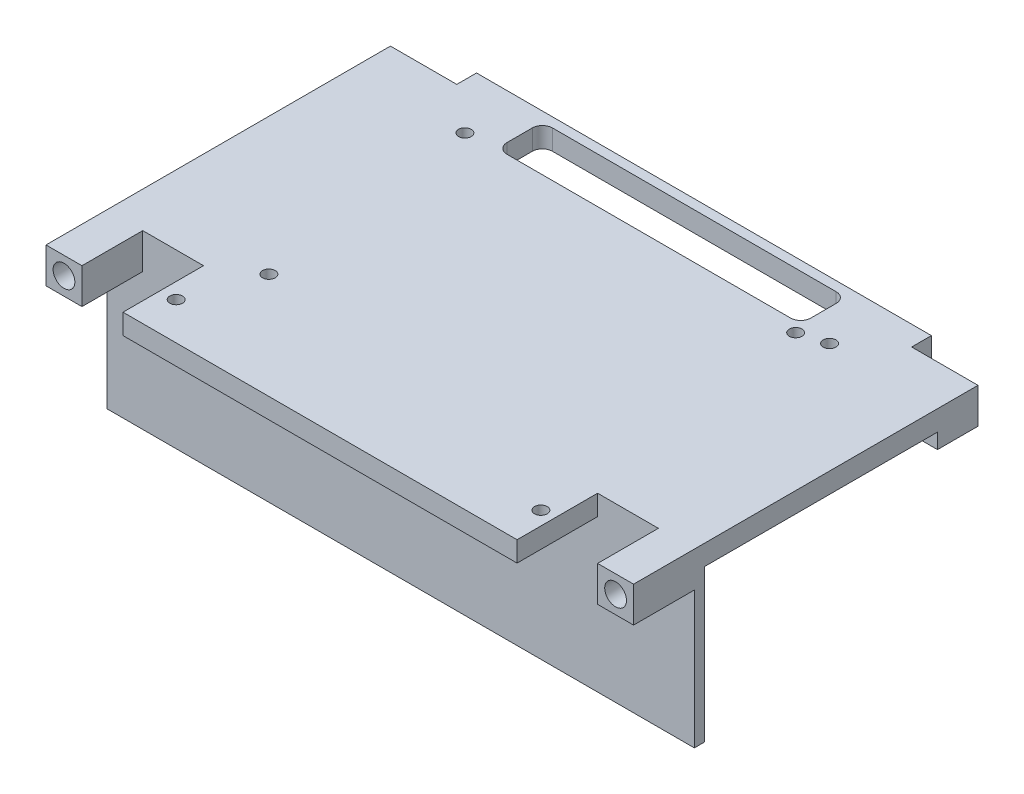
SolidWorks part; units mm, degrees
ref_plane "Front Plane" through (0, 0, 0) normal (0, 0, 1) x (1, 0, 0)
ref_plane "Top Plane" through (0, 0, 0) normal (0, 1, 0) x (1, 0, 0)
ref_plane "Right Plane" through (0, 0, 0) normal (1, 0, 0) x (0, 0, -1)
sketch "Sketch1" plane through (0, 0, 0) normal (0, 1, 0) x (1, 0, 0)
  line L0 (-58, 0) -> (58, 0) construction
  line L1 (-58, -34) -> (-50.9, -34)
  line L2 (-58, -34) -> (-58, 34)
  line L3 (-58, 34) -> (-50.9, 34)
  line L4 (58, -34) -> (58, 34)
  line L5 (-58, -34) -> (58, 34) construction
  line L6 (-58, 34) -> (58, -34) construction
  line L8 (-50.9, 34) -> (-50.9, 41)
  line L9 (-50.9, 41) -> (50.9, 41)
  line L10 (50.9, 34) -> (50.9, 41)
  line L11 (50.9, 34) -> (58, 34)
  line L12 (50.9, -34) -> (50.9, -41)
  line L13 (-50.9, -41) -> (50.9, -41)
  line L14 (-50.9, -34) -> (-50.9, -41)
  line L15 (50.9, -34) -> (58, -34)
  point P0 (0, 0)
  point P10 (0, 41)
  dimension "D1" = 116
  dimension "D2" = 68
  dimension "D3" = 7.1
  dimension "D4" = 7
extrude "Boss-Extrude1" add sketch "Sketch1" along normal blind 4
sketch "Sketch3" plane through (0, 0, 0) normal (0, -1, 0) x (1, 0, 0)
  line L0 (-58, -34) -> (-58, 34) construction
  line L1 (-50.9, -34) -> (-58, -34)
  line L2 (-50.9, -34) -> (-50.9, -26)
  line L3 (-50.9, -26) -> (-58, -26)
  line L4 (-58, -34) -> (-58, -26)
  dimension "D1" = 8
extrude "Boss-Extrude3" add sketch "Sketch3" along normal blind 3
sketch "Sketch4" plane through (0, 0, -34) normal (0, 0, -1) x (-1, 0, 0)
  line L0 (58, -3) -> (50.9, 4) construction
  circle A0 centre (54.45, 0.5) radius 2.15
  dimension "D1" = 4.3
extrude "Cut-Extrude1" cut sketch "Sketch4" against normal blind 7
mirror "Mirror1" about plane through (0, 0, 0) normal (1, 0, 0) of "Cut-Extrude1", "Boss-Extrude3"
mirror "Mirror2" about plane through (0, 0, 0) normal (0, 0, 1) of "Cut-Extrude1", "Boss-Extrude3", "Mirror1"
sketch "Sketch5" plane through (0, 4, 0) normal (0, 1, 0) x (1, 0, 0)
  line L0 (50.9, 41) -> (-50.9, 41) construction
  line L1 (-30, 36) -> (30, 36)
  line L2 (-30, 36) -> (-30, 27)
  line L3 (-30, 27) -> (30, 27)
  line L4 (30, 36) -> (30, 27)
  point P4 (0, 27)
  dimension "D1" = 5
  dimension "D2" = 9
  dimension "D3" = 60
extrude "Cut-Extrude2" cut sketch "Sketch5" against normal through all
sketch "Sketch6" plane through (0, 4, 0) normal (0, 1, 0) x (1, 0, 0)
  line L1 (-38.5, -28) -> (38.5, -28) construction
  line L2 (-38.5, -28) -> (-38.5, 24) construction
  line L3 (-38.5, 24) -> (38.5, 24) construction
  line L4 (38.5, -28) -> (38.5, 24) construction
  line L5 (-38.5, -28) -> (38.5, 24) construction
  line L6 (-38.5, 24) -> (38.5, -28) construction
  circle A0 centre (-38.5, 24) radius 1.25
  circle A1 centre (38.5, 24) radius 1.25
  circle A2 centre (38.5, -28) radius 1.25
  circle A3 centre (-38.5, -28) radius 1.25
  point P0 (0, -2)
  point P9 (0, -2)
  dimension "D4" = 2.5
  dimension "D1" = 77
  dimension "D2" = 52
  dimension "D3" = 2
fillet "Fillet1" radius 2 4 edges at (-30, 2, -36) (-30, 2, -27) (30, 2, -36) (30, 2, -27)
sketch "Sketch7" plane through (0, 4, 0) normal (0, 1, 0) x (1, 0, 0)
  line L0 (50.9, 34) -> (50.9, 41) construction
  line L1 (-50.9, 41) -> (50.9, 41)
  line L2 (-50.9, 41) -> (-50.9, 40)
  line L3 (-50.9, 40) -> (50.9, 40)
  line L4 (50.9, 41) -> (50.9, 40)
  line L5 (-50.9, -34) -> (-50.9, -41) construction
  line L6 (50.9, -41) -> (-50.9, -41)
  line L7 (50.9, -41) -> (50.9, -40)
  line L8 (50.9, -40) -> (-50.9, -40)
  line L9 (-50.9, -41) -> (-50.9, -40)
  dimension "D1" = 1
  dimension "D2" = 1
extrude "Cut-Extrude3" cut sketch "Sketch7" against normal through all
sketch "Sketch8" plane through (0, 0, 0) normal (0, -1, 0) x (1, 0, 0)
  line L0 (58, 26) -> (58, -26) construction
  line L1 (58, 22) -> (-58, 22)
  line L2 (58, 22) -> (58, 20)
  line L3 (58, 20) -> (-58, 20)
  line L4 (-58, 22) -> (-58, 20)
  line L5 (-58, -26) -> (-58, 26) construction
  line L7 (50.9, 40) -> (-50.9, 40) construction
  dimension "D1" = 20
  dimension "D2" = 2
extrude "Boss-Extrude4" add sketch "Sketch8" along normal blind 30
sketch "Sketch9" plane through (0, 4, 0) normal (0, 1, 0) x (1, 0, 0)
  line L0 (58, -22) -> (-58, -22) construction
  line L1 (-50.9, -40) -> (-38.9, -40)
  line L2 (-50.9, -40) -> (-50.9, -22)
  line L3 (-50.9, -22) -> (-38.9, -22)
  line L4 (-38.9, -40) -> (-38.9, -22)
  dimension "D1" = 12
extrude "Cut-Extrude4" cut sketch "Sketch9" against normal blind 10
sketch "Sketch10" plane through (0, -3, 0) normal (0, -1, 0) x (1, 0, 0)
  line L1 (-58, 26) -> (-50.9, 26)
  line L2 (-58, 26) -> (-58, 22)
  line L3 (-58, 22) -> (-50.9, 22)
  line L4 (-50.9, 26) -> (-50.9, 22)
  line L5 (50.9, 26) -> (58, 26)
  line L6 (50.9, 26) -> (50.9, 22)
  line L7 (50.9, 22) -> (58, 22)
  line L8 (58, 26) -> (58, 22)
extrude "Boss-Extrude5" add sketch "Sketch10" against normal up to surface (3 mm away) up to face at (27.2714, 0, 30)
ref_plane "Plane2" through (-51, 0, 0) normal (-1, 0, 0) x (0, 0, 1)
sketch "Sketch12" plane through (-51, 0, 0) normal (-1, 0, 0) x (0, 0, 1)
  line L0 (22, -5.8) -> (22, -16.2)
  line L1 (22, -30) -> (22, -3) construction
  line L2 (22, -16.2) -> (24.7, -13.5)
  line L3 (24.7, -13.5) -> (24.7, -8.5)
  line L4 (24.7, -8.5) -> (22, -5.8)
  line L5 (24.7, -11) -> (22, -11) construction
  line L6 (22, -3) -> (34, -3) construction
  line L7 (24.1, -9) -> (22.6, -9)
  line L8 (24.1, -9) -> (24.1, -13)
  line L9 (24.1, -13) -> (22.6, -13)
  line L10 (22.6, -9) -> (22.6, -13)
  line L11 (22, -20.8) -> (22, -31.2)
  line L12 (22, -31.2) -> (24.7, -28.5)
  line L13 (24.7, -28.5) -> (24.7, -23.5)
  line L14 (24.7, -23.5) -> (22, -20.8)
  line L15 (24.1, -24) -> (22.6, -24)
  line L16 (24.1, -24) -> (24.1, -28)
  line L17 (24.1, -28) -> (22.6, -28)
  line L18 (22.6, -24) -> (22.6, -28)
  line L19 (24.7, -26) -> (22, -26) construction
  point P13 (23.35, -11)
  point P14 (24.1, -11)
  dimension "D1" = 1.5
  dimension "D2" = 0.6
  dimension "D3" = 0.6
  dimension "D4" = 4
  dimension "D5" = 45
  dimension "D6" = 5
  dimension "D7" = 8
  dimension "D8" = 2
extrude "Boss-Extrude6" add sketch "Sketch12" against normal blind 2
ref_plane "Plane3" through (-44.9, 0, 0) normal (1, 0, 0) x (0, 0, -1)
mirror "Mirror3" about plane through (-44.9, 0, 0) normal (1, 0, 0) of "Boss-Extrude6"
sketch "Sketch13" plane through (0, 0, 0) normal (0, -1, 0) x (1, 0, 0)
  line L0 (-28, -27) -> (28, -27) construction
  line L1 (-18, -17.5) -> (18, -17.5)
  line L2 (-18, -17.5) -> (-18, -19.5)
  line L3 (-18, -19.5) -> (18, -19.5)
  line L4 (18, -17.5) -> (18, -19.5)
  point P4 (0, -19.5)
  dimension "D1" = 36
  dimension "D2" = 2
  dimension "D3" = 7.5
extrude "Boss-Extrude7" add sketch "Sketch13" along normal up to surface (30 mm away) up to face at (-22.45, -30, 21.5)
sketch "Sketch14" plane through (0, 0, 0) normal (1, 0, 0) x (0, 0, -1)
  line L3 (-0.25, -38) -> (-0.25, 0) construction
  line L4 (-20, 0) -> (26, 0) construction
  line L13 (-24.1, -13) -> (-24.1, -9) construction
  line L14 (-24.1, -9) -> (-22.6, -9) construction
  line L15 (-22.6, -9) -> (-22.6, -13) construction
  line L16 (-22.6, -13) -> (-24.1, -13) construction
  line L17 (-22, -5.8) -> (-22, -16.2) construction
  line L18 (-22, -16.2) -> (-24.7, -13.5) construction
  line L19 (-24.7, -13.5) -> (-24.7, -8.5) construction
  line L20 (-24.7, -8.5) -> (-22, -5.8) construction
  line L29 (-24.1, -13) -> (-24.1, -9) construction
  line L30 (-24.1, -9) -> (-22.6, -9) construction
  line L31 (-22.6, -9) -> (-22.6, -13) construction
  line L32 (-22.6, -13) -> (-24.1, -13) construction
  line L33 (-22, -5.8) -> (-22, -16.2) construction
  line L34 (-22, -16.2) -> (-24.7, -13.5) construction
  line L35 (-24.7, -13.5) -> (-24.7, -8.5) construction
  line L36 (-24.7, -8.5) -> (-22, -5.8) construction
  line L37 (24.2, -8.5) -> (21.5, -5.8)
  line L38 (24.2, -13.5) -> (24.2, -8.5)
  line L39 (21.5, -16.2) -> (24.2, -13.5)
  line L40 (21.5, -5.8) -> (21.5, -16.2)
  line L41 (22.1, -13) -> (23.6, -13)
  line L42 (22.1, -9) -> (22.1, -13)
  line L43 (23.6, -9) -> (22.1, -9)
  line L44 (23.6, -13) -> (23.6, -9)
extrude "Boss-Extrude8" add sketch "Sketch14" along normal mid plane 2
sketch "Sketch15" plane through (0, 0, 0) normal (1, 0, 0) x (0, 0, -1)
  line L0 (17.5, 0) -> (17.5, -5)
  line L1 (17.5, -30) -> (17.5, 0) construction
  line L2 (17.5, -5) -> (14.6132, 0)
  line L3 (-20, 0) -> (26, 0) construction
  line L4 (14.6132, 0) -> (17.5, 0)
  dimension "D1" = 60
  dimension "D2" = 5
extrude "Boss-Extrude9" add sketch "Sketch15" against normal up to surface and the other way up to surface up to face at (-18, -15, -18.5) other way up to face at (18, -15, -18.5)
sketch "Sketch16" plane through (0, 0, 40) normal (0, 0, 1) x (1, 0, 0)
  line L0 (38, 0) -> (18, -28) construction
  line L1 (38, 0) -> (18, 0)
  line L2 (38, 0) -> (38, -28)
  line L3 (38, -28) -> (18, -28)
  line L4 (18, 0) -> (18, -28)
  line L5 (50.9, 0) -> (-38.9, 0) construction
  line L6 (20.7, -15.8) -> (35.3, -15.8)
  line L7 (20.7, -15.8) -> (20.7, -25)
  line L8 (20.7, -25) -> (35.3, -25)
  line L9 (35.3, -15.8) -> (35.3, -25)
  line L10 (20.7, -15.8) -> (35.3, -25) construction
  line L11 (20.7, -25) -> (35.3, -15.8) construction
  line L12 (58, -30) -> (58, -3) construction
  point P5 (28, -14)
  point P10 (28, -20.4)
  dimension "D1" = 20
  dimension "D2" = 28
  dimension "D3" = 14.6
  dimension "D4" = 9.2
  dimension "D5" = 20
  dimension "D6" = 3
extrude "Boss-Extrude10" add sketch "Sketch16" against normal blind 2.6
sketch "Sketch17" plane through (0, 0, 0) normal (0, -1, 0) x (1, 0, 0)
  line L6 (-38.9, 22) -> (-50.9, 22) construction
  line L7 (50.9, 40) -> (38.9, 40)
  line L8 (50.9, 40) -> (50.9, 22)
  line L9 (50.9, 22) -> (38.9, 22)
  line L10 (38.9, 40) -> (38.9, 22)
  line L13 (-38.9, 40) -> (-38.9, 22) construction
extrude "Cut-Extrude5" cut sketch "Sketch17" against normal through all
sketch "Sketch18" plane through (0, 4, 0) normal (0, 1, 0) x (1, 0, 0)
  line L5 (-50.9, 40) -> (50.9, 40) construction
  line L6 (50.9, 34) -> (44.9, 34)
  line L7 (50.9, 34) -> (50.9, 40)
  line L8 (50.9, 40) -> (44.9, 40)
  line L9 (44.9, 34) -> (44.9, 40)
  line L11 (-50.9, 34) -> (-44.9, 34)
  line L12 (-50.9, 34) -> (-50.9, 40)
  line L13 (-50.9, 40) -> (-44.9, 40)
  line L14 (-44.9, 34) -> (-44.9, 40)
extrude "Cut-Extrude6" cut sketch "Sketch18" against normal through all
sketch "Sketch20" plane through (0, 4, 0) normal (0, 1, 0) x (1, 0, 0)
  line L0 (-31, 25) -> (31, -17) construction
  line L1 (-31, 25) -> (31, 25) construction
  line L2 (-31, 25) -> (-31, -17) construction
  line L3 (-31, -17) -> (31, -17) construction
  line L4 (31, 25) -> (31, -17) construction
  line L5 (-38.5, 26) -> (38.5, 26) construction
  line L6 (-38.5, 26) -> (-38.5, -26) construction
  line L7 (-38.5, -26) -> (38.5, -26) construction
  line L8 (38.5, 26) -> (38.5, -26) construction
  line L11 (38.5, 26) -> (-38.5, -26) construction
  circle A0 centre (-31, 25) radius 3 construction
  circle A1 centre (-31, -17) radius 3 construction
  circle A2 centre (31, -17) radius 3 construction
  circle A3 centre (31, 25) radius 3 construction
  circle A4 centre (-38.5, 26) radius 3 construction
  circle A5 centre (38.5, 26) radius 3 construction
  circle A6 centre (38.5, -26) radius 3 construction
  circle A7 centre (-38.5, -26) radius 3 construction
  point P18 (0, 4)
  dimension "D3" = 6
  dimension "D1" = 42
  dimension "D2" = 62
  dimension "D4" = 4
  dimension "D6" = 77
  dimension "D7" = 52
sketch "Sketch22" plane through (0, 4, 0) normal (0, 1, 0) x (1, 0, 0)
  circle A0 centre (-31, 25) radius 1.25 construction
  circle A1 centre (31, 25) radius 1.25
  circle A2 centre (31, -17) radius 1.25 construction
  circle A3 centre (-31, -17) radius 1.25
  dimension "D1" = 2.5
extrude "Cut-Extrude7" cut sketch "Sketch22" against normal up to surface (4 mm away) up to face at (14, 0, 34.85)
sketch "Sketch25" plane through (0, 0, -19.5) normal (0, 0, -1) x (-1, 0, 0)
  line L0 (58, -30) -> (-58, -30) construction
  line L1 (-18, -30) -> (-12, -30)
  line L2 (-18, -30) -> (-18, 0)
  line L3 (-18, 0) -> (-12, 0)
  line L4 (-12, -30) -> (-12, 0)
  line L5 (-18, -30) -> (-18, 0) construction
  line L6 (18, 0) -> (-18, 0) construction
  line L7 (-18, -30) -> (18, -30) construction
  line L8 (18, 0) -> (12, 0)
  line L9 (18, 0) -> (18, -30)
  line L10 (18, -30) -> (12, -30)
  line L11 (12, 0) -> (12, -30)
  dimension "D1" = 6
extrude "Cut-Extrude11" cut sketch "Sketch25" against normal blind 10
sketch "Sketch26" plane through (-1, 0, 0) normal (-1, 0, 0) x (0, 0, 1)
  line L1 (-20.3582, -5.0992) -> (-27.2016, -5.0992)
  line L2 (-20.3582, -5.0992) -> (-20.3582, -36.3625)
  line L3 (-20.3582, -36.3625) -> (-27.2016, -36.3625)
  line L4 (-27.2016, -5.0992) -> (-27.2016, -36.3625)
  line L5 (22, -5.8) -> (28.5342, -5.8)
  line L6 (22, -5.8) -> (22, -34.3243)
  line L7 (22, -34.3243) -> (28.5342, -34.3243)
  line L8 (28.5342, -5.8) -> (28.5342, -34.3243)
extrude "Cut-Extrude12" cut sketch "Sketch26" against normal through all both and the other way through all
sketch "Sketch27" plane through (0, 4, 0) normal (0, 1, 0) x (1, 0, 0)
  line L1 (-35.8, -30.5) -> (36.2, -30.5) construction
  line L2 (-35.8, -30.5) -> (-35.8, 26.5) construction
  line L3 (-35.8, 26.5) -> (36.2, 26.5) construction
  line L4 (36.2, -30.5) -> (36.2, 26.5) construction
  line L5 (-35.8, -30.5) -> (36.2, 26.5) construction
  line L6 (-35.8, 26.5) -> (36.2, -30.5) construction
  circle A0 centre (-35.8, 26.5) radius 1.25
  circle A1 centre (-35.8, -30.5) radius 1.25
  circle A2 centre (36.2, -30.5) radius 1.25
  circle A3 centre (36.2, 26.5) radius 1.25
  circle A5 centre (31, 25) radius 1.25 construction
  circle A6 centre (31, 25) radius 1.25 construction
  point P0 (0.2, -2)
  dimension "D1" = 72
  dimension "D2" = 57
  dimension "D3" = 2
  dimension "D4" = 0.2
extrude "Cut-Extrude13" cut sketch "Sketch27" against normal through all
sketch "Sketch28" plane through (0, 4, 0) normal (0, 1, 0) x (1, 0, 0)
  line L0 (44.9, 40) -> (44.9, 34) construction
  line L1 (-44.9, 40) -> (44.9, 40)
  line L2 (-44.9, 40) -> (-44.9, 39.4)
  line L3 (-44.9, 39.4) -> (44.9, 39.4)
  line L4 (44.9, 40) -> (44.9, 39.4)
  line L5 (-38.9, -40) -> (-38.9, -22) construction
  line L6 (38.9, -40) -> (-38.9, -40)
  line L7 (38.9, -40) -> (38.9, -39.4)
  line L8 (38.9, -39.4) -> (-38.9, -39.4)
  line L9 (-38.9, -40) -> (-38.9, -39.4)
  dimension "D1" = 0.6
  dimension "D2" = 0.6
extrude "Cut-Extrude14" cut sketch "Sketch28" against normal through all
chamfer "Chamfer1" distance 2 angle 45 1 edges at (28, 0, 37.4)
sketch "Sketch29" plane through (0, 0, 39.4) normal (0, 0, 1) x (1, 0, 0)
  line L1 (18, -28) -> (38, -28)
  line L2 (18, -28) -> (18, 0)
  line L3 (18, 0) -> (38, 0)
  line L4 (38, -28) -> (38, 0)
extrude "Cut-Extrude15" cut sketch "Sketch29" against normal up to surface (17.4 mm away) up to face at (0, -4.6667, 22)
sketch "Sketch30" plane through (0, 4, 0) normal (0, 1, 0) x (1, 0, 0)
  line L0 (44.9, 39.4) -> (44.9, 34) construction
  line L1 (-44.9, 39.4) -> (44.9, 39.4)
  line L2 (-44.9, 39.4) -> (-44.9, 37.9)
  line L3 (-44.9, 37.9) -> (44.9, 37.9)
  line L4 (44.9, 39.4) -> (44.9, 37.9)
  line L5 (-38.9, -39.4) -> (-38.9, -22) construction
  line L6 (38.9, -39.4) -> (-38.9, -39.4)
  line L7 (38.9, -39.4) -> (38.9, -37.9)
  line L8 (38.9, -37.9) -> (-38.9, -37.9)
  line L9 (-38.9, -39.4) -> (-38.9, -37.9)
  dimension "D1" = 1.5
  dimension "D2" = 1.5
sketch "Sketch31" plane through (-1, 0, 0) normal (-1, 0, 0) x (0, 0, 1)
  line L4 (-24.2, -8.5) -> (-24.2, -13.5)
  line L5 (-24.2, -13.5) -> (-21.5, -16.2)
  line L6 (-21.5, -16.2) -> (-21.5, -5.8)
  line L7 (-21.5, -5.8) -> (-24.2, -8.5)
  line L8 (-24.2, -8.5) -> (-24.2, -13.5)
  line L9 (-24.2, -13.5) -> (-21.5, -16.2)
  line L10 (-21.5, -16.2) -> (-21.5, -5.8)
  line L11 (-21.5, -5.8) -> (-24.2, -8.5)
  dimension "D1" = 0
extrude "Cut-Extrude16" cut sketch "Sketch31" against normal up to surface (2 mm away) up to face at (1, -11, -22.85)
extrude "Cut-Extrude17" cut sketch "Sketch30" against normal through all
sketch "Sketch32" plane through (0, 0, -19.5) normal (0, 0, -1) x (-1, 0, 0)
  line L0 (44.9, 0) -> (-44.9, 0) construction
  line L1 (-7, -12) -> (7, -12)
  line L2 (-7, -12) -> (-7, -18)
  line L3 (-7, -18) -> (7, -18)
  line L4 (7, -12) -> (7, -18)
  point P4 (0, -12)
  dimension "D1" = 14
  dimension "D2" = 6
  dimension "D3" = 12
extrude "Boss-Extrude11" add sketch "Sketch32" along normal blind 1
chamfer "Chamfer2" distance 1 angle 45 1 edges at (0, -12, -19.5)
sketch "Sketch33" plane through (0, 0, -20.5) normal (0, 0, -1) x (-1, 0, 0)
  line L0 (-7, -12) -> (7, -18) construction
  line L1 (-4, -15) -> (4, -15) construction
  circle A0 centre (4, -15) radius 1.65
  circle A1 centre (-4, -15) radius 1.65
  point P7 (0, -15)
  dimension "D2" = 3.3
  dimension "D1" = 8
sketch "Sketch34" plane through (0, 0, -17.5) normal (0, 0, 1) x (1, 0, 0)
  line L4 (7, -18) -> (7, -12)
  line L5 (-7, -18) -> (7, -18)
  line L6 (-7, -12) -> (-7, -18)
  line L7 (7, -12) -> (-7, -12)
  line L8 (7, -18) -> (7, -12)
  line L9 (-7, -18) -> (7, -18)
  line L10 (-7, -12) -> (-7, -18)
  line L11 (7, -12) -> (-7, -12)
  dimension "D1" = 0
extrude "Boss-Extrude12" add sketch "Sketch34" along normal blind 3
chamfer "Chamfer3" distance 3 angle 45 1 edges at (0, -12, -17.5)
extrude "Cut-Extrude18" cut sketch "Sketch33" against normal up to surface (6 mm away) up to face at (0, -15, -14.5)
chamfer "Chamfer4" distance 3 angle 45 1 edges at (0, 0, -19.5)
